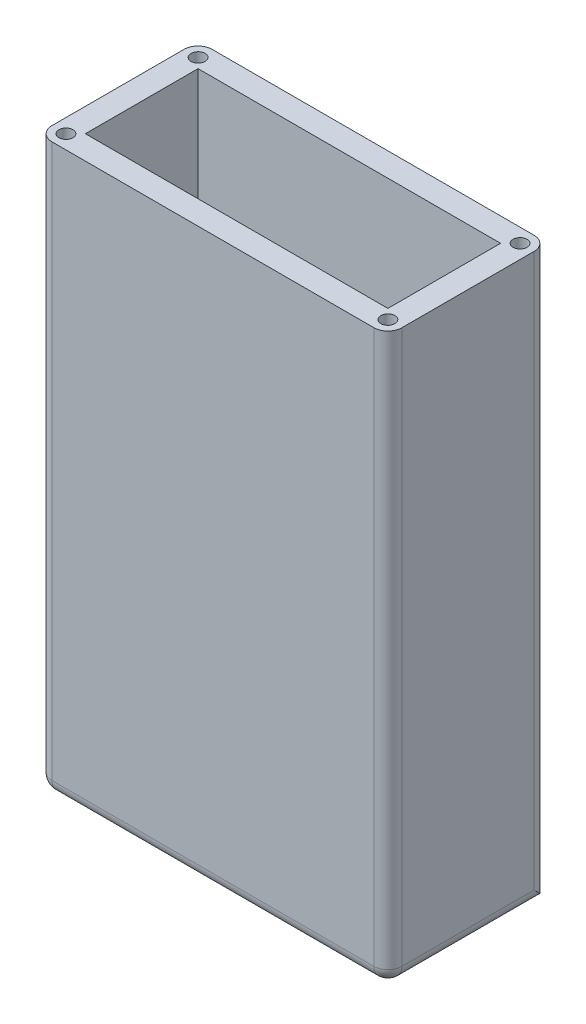
SolidWorks part; units mm, degrees
ref_plane "Front Plane" through (0, 0, 0) normal (0, 0, 1) x (1, 0, 0)
ref_plane "Top Plane" through (0, 0, 0) normal (0, 1, 0) x (1, 0, 0)
ref_plane "Right Plane" through (0, 0, 0) normal (1, 0, 0) x (0, 0, -1)
sketch "Sketch1" plane through (0, 0, 0) normal (0, 1, 0) x (1, 0, 0)
  line L1 (0, 0) -> (74.93, 0)
  line L2 (0, 0) -> (0, 34.29)
  line L3 (0, 34.29) -> (74.93, 34.29)
  line L4 (74.93, 0) -> (74.93, 34.29)
  dimension "D1" = 74.93
  dimension "D2" = 34.29
extrude "Boss-Extrude1" add sketch "Sketch1" along normal blind 87.122
shell "Shell1" thickness 2.54 removed face at (37.465, 43.561, -34.29)
sketch "Sketch12" plane through (0, 87.122, 0) normal (0, 1, 0) x (1, 0, 0)
  line L1 (0, 0) -> (74.93, 0)
  line L2 (0, 0) -> (0, 34.29)
  line L3 (0, 34.29) -> (74.93, 34.29)
  line L4 (74.93, 0) -> (74.93, 34.29)
extrude "Boss-Extrude6" add sketch "Sketch12" along normal blind 34.29
shell "Shell2" thickness 5.08 removed face at (37.465, 121.412, -17.145)
sketch "Sketch18" plane through (0, 89.662, 0) normal (0, 1, 0) x (1, 0, 0)
  line L0 (5.08, 5.08) -> (69.85, 5.08) construction
  line L1 (34.925, 5.08) -> (22.225, 5.08)
  line L2 (34.925, 5.08) -> (34.925, 14.605)
  line L3 (34.925, 14.605) -> (22.225, 14.605)
  line L4 (22.225, 5.08) -> (22.225, 14.605)
  line L5 (69.85, 5.08) -> (69.85, 29.21) construction
  line L6 (69.85, 29.21) -> (5.08, 29.21) construction
  line L7 (69.85, 22.21) -> (64.85, 22.21)
  line L8 (69.85, 22.21) -> (69.85, 12.08)
  line L9 (69.85, 12.08) -> (64.85, 12.08)
  line L10 (64.85, 22.21) -> (64.85, 12.08)
  dimension "D1" = 34.925
  dimension "D2" = 47.625
  dimension "D3" = 9.525
  dimension "D4" = 5
  dimension "D5" = 7
  dimension "D6" = 7
extrude "Cut-Extrude13" cut sketch "Sketch18" against normal up to next
sketch "Sketch20" plane through (0, 121.412, 0) normal (0, 1, 0) x (1, 0, 0)
  line L0 (0, 34.29) -> (0, 0) construction
  line L2 (74.93, 34.29) -> (0, 34.29) construction
  line L3 (0, 0) -> (74.93, 0) construction
  line L4 (74.93, 0) -> (74.93, 34.29) construction
  circle A0 centre (3, 31.29) radius 1.5
  circle A1 centre (3, 3) radius 1.5
  circle A2 centre (71.93, 3) radius 1.5
  circle A3 centre (71.93, 31.29) radius 1.5
  point P8 (0, 0)
  point P9 (0, 0)
  point P10 (0, 0)
  point P13 (0, 0)
  point P15 (7.3304, 34.29)
  dimension "D1" = 3
  dimension "D2" = 3
  dimension "D3" = 3
  dimension "D4" = 3
  dimension "D5" = 3
  dimension "D6" = 3
  dimension "D7" = 3
  dimension "D8" = 3
extrude "Cut-Extrude14" cut sketch "Sketch20" against normal blind 20
fillet "Fillet1" radius 3 7 edges at (74.93, 0, -17.145) (0, 0, -17.145) (37.465, 0, 0) (74.93, 60.706, -34.29) (0, 60.706, -34.29) (74.93, 60.706, 0) (0, 60.706, 0)
